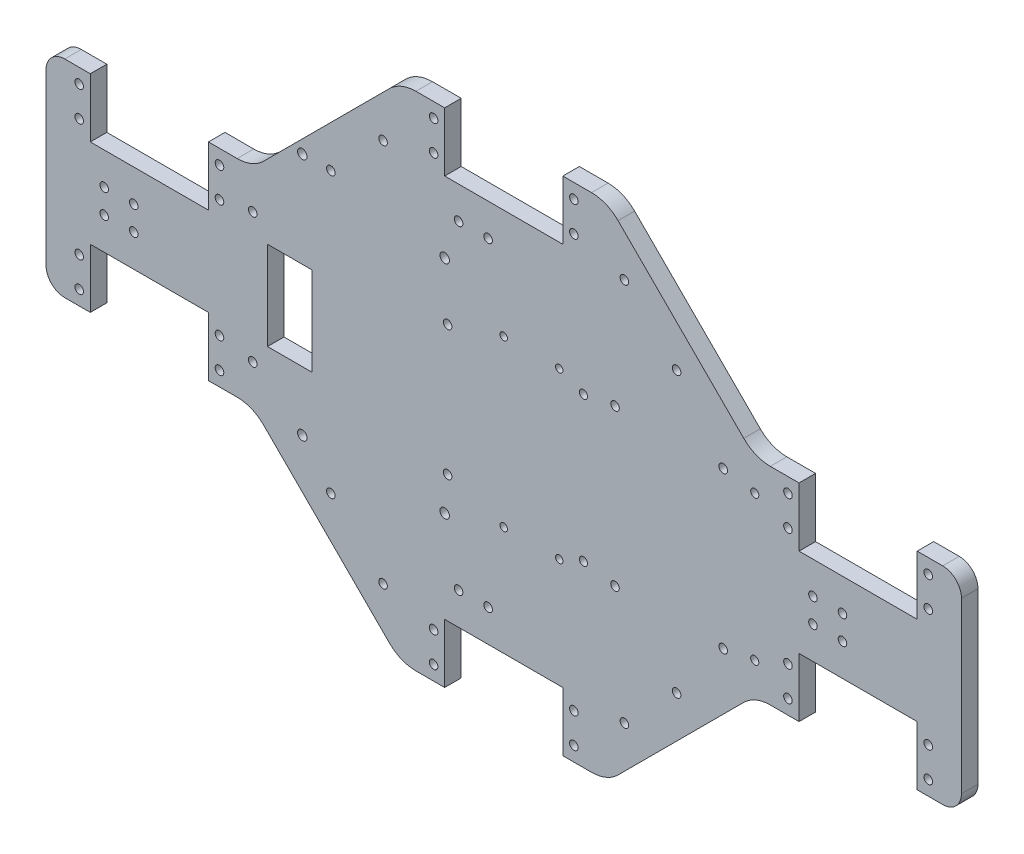
SolidWorks part; units mm, degrees
material "ABS"
ref_plane "Front" through (0, 0, 0) normal (0, 0, 1) x (1, 0, 0)
ref_plane "Top" through (0, 0, 0) normal (0, 1, 0) x (1, 0, 0)
ref_plane "Right" through (0, 0, 0) normal (1, 0, 0) x (0, 0, -1)
sketch "Esquisse1" plane through (0, 0, 0) normal (0, 0, 1) x (1, 0, 0)
  line L0 (70, -35) -> (120, -85)
  line L1 (0, 0) -> (25.8386, 0)
  line L2 (0, 0) -> (0, -35)
  line L3 (0, -35) -> (70, -35)
  line L5 (0, 0) -> (70, -35) construction
  line L6 (0, -35) -> (25.8386, 0) construction
  line L7 (120, -85) -> (190, -85)
  line L8 (190, -85) -> (240, -35)
  line L9 (240, -35) -> (310, -35)
  line L10 (310, -35) -> (310, 0)
  line L11 (310, 0) -> (25.8386, 0)
  point P0 (0, 0)
  dimension "D1" = 70
  dimension "D2" = 70
  dimension "D3" = 70
  dimension "D4" = 135
  dimension "D5" = 135
  dimension "D6" = 0
  dimension "D7" = 50
  dimension "D8" = 35
extrude "Boss.-Extru.1" add sketch "Esquisse1" along normal blind 5.6
sketch "Esquisse2" plane through (0, 0, 5.6) normal (0, 0, 1) x (1, 0, 0)
  line L0 (0, -35) -> (70, -35) construction
  line L1 (15, -15) -> (55, -15)
  line L2 (15, -15) -> (15, -35)
  line L3 (15, -35) -> (55, -35)
  line L4 (55, -15) -> (55, -35)
  line L5 (15, -15) -> (55, -35) construction
  line L6 (15, -35) -> (55, -15) construction
  line L7 (0, 0) -> (0, -35) construction
  point P0 (0, -90)
  dimension "D1" = 20
  dimension "D2" = 40
  dimension "D3" = 15
extrude "Enlèv. mat.-Extru.1" cut sketch "Esquisse2" against normal up to next
sketch "Esquisse3" plane through (0, 0, 5.6) normal (0, 0, 1) x (1, 0, 0)
  line L0 (15, -25) -> (55, -25) construction
  line L1 (15, -15) -> (15, -35) construction
  line L2 (55, -35) -> (55, -15) construction
  circle A0 centre (11.25, -30.08) radius 1.45
  circle A1 centre (58.75, -30.08) radius 1.45
  circle A2 centre (58.75, -19.92) radius 1.45
  circle A3 centre (11.25, -19.92) radius 1.45
  circle A4 centre (19.712, -4.09) radius 1.45
  circle A5 centre (29.712, -4.09) radius 1.45
  dimension "D1" = 3.75
  dimension "D2" = 5.08
  dimension "D3" = 47.5
  dimension "D4" = 2.9
  dimension "D5" = 3.75
  dimension "D6" = 2.9
  dimension "D7" = 2.9
  dimension "D8" = 10
  dimension "D9" = 8.462
  dimension "D10" = 15.83
  dimension "D11" = 0
extrude "Enlèv. mat.-Extru.2" cut sketch "Esquisse3" against normal up to next
sketch "Sketch2" plane through (0, 0, 0) normal (0, 0, 1) x (1, 0, 0)
  line L0 (120, -85) -> (190, -85) construction
  line L1 (255, -15) -> (295, -15)
  line L2 (255, -15) -> (255, -35)
  line L3 (255, -35) -> (295, -35)
  line L4 (295, -15) -> (295, -35)
  line L5 (255, -15) -> (295, -35) construction
  line L6 (255, -35) -> (295, -15) construction
  line L7 (240, -35) -> (310, -35) construction
  line L8 (310, -35) -> (310, 0) construction
  line L9 (135, -65) -> (175, -65)
  line L10 (135, -65) -> (135, -85)
  line L11 (135, -85) -> (175, -85)
  line L12 (175, -65) -> (175, -85)
  line L13 (135, -65) -> (175, -85) construction
  line L14 (135, -85) -> (175, -65) construction
  point P0 (0, -90)
  point P11 (-35, 0)
  dimension "D1" = 20
  dimension "D2" = 40
  dimension "D3" = 15
  dimension "D4" = 40
  dimension "D5" = 20
  dimension "D6" = 15
extrude "Cut-Extrude2" cut sketch "Sketch2" against normal through all and the other way through all
sketch "Sketch5" plane through (0, 0, 0) normal (0, 0, 1) x (1, 0, 0)
  line L0 (180, -75) -> (175, -75) construction
  line L1 (175, -85) -> (175, -65) construction
  line L2 (255, -25) -> (295, -25) construction
  line L4 (295, -35) -> (295, -15) construction
  line L5 (255, -15) -> (255, -35) construction
  circle A0 centre (131.25, -80.08) radius 1.45
  circle A1 centre (178.75, -80.08) radius 1.45
  circle A2 centre (178.75, -69.92) radius 1.45
  circle A3 centre (131.25, -69.92) radius 1.45
  circle A4 centre (251.25, -30.08) radius 1.45
  circle A5 centre (298.75, -30.08) radius 1.45
  circle A6 centre (298.75, -19.92) radius 1.45
  circle A7 centre (251.25, -19.92) radius 1.45
  circle A8 centre (139.712, -54.09) radius 1.45
  circle A9 centre (149.712, -54.09) radius 1.45
  circle A10 centre (259.712, -4.09) radius 1.45
  circle A11 centre (269.712, -4.09) radius 1.45
  dimension "D1" = 5.08
  dimension "D2" = 5.08
  dimension "D3" = 47.5
  dimension "D4" = 2.9
  dimension "D5" = 3.75
  dimension "D10" = 2.9
  dimension "D11" = 2.9
  dimension "D12" = 2.9
  dimension "D16" = 2.9
  dimension "D17" = 2.9
  dimension "D6" = 5.08
  dimension "D7" = 5.08
  dimension "D8" = 3.75
  dimension "D9" = 3.75
  dimension "D13" = 10
  dimension "D14" = 8.462
  dimension "D15" = 15.83
  dimension "D18" = 8.462
  dimension "D19" = 15.83
  dimension "D20" = 10
  dimension "D21" = 0
  dimension "D22" = 0
extrude "Cut-Extrude4" cut sketch "Sketch5" along normal through all
mirror "Mirror1" about plane through (0, 0, 0) normal (0, 1, 0) of "Cut-Extrude4", "Cut-Extrude2", "Enlèv. mat.-Extru.1", "Enlèv. mat.-Extru.2", "Boss.-Extru.1"
sketch "Esquisse4" plane through (0, 0, 5.6) normal (0, 0, 1) x (1, 0, 0)
  line L0 (182, 24.5) -> (240, 24.5) construction
  line L1 (240, 24.5) -> (240, -24.5) construction
  line L2 (240, -24.5) -> (182, -24.5) construction
  line L3 (0, 0) -> (310, 0) construction
  line L4 (0, 35) -> (0, -35) construction
  line L5 (310, -35) -> (310, 35) construction
  line L6 (255, 15) -> (255, 35) construction
  circle A0 centre (182, -24.5) radius 1.375
  circle A4 centre (240, -24.5) radius 1.375
  circle A5 centre (240, 24.5) radius 1.375
  circle A6 centre (182, 24.5) radius 1.375
  point P14 (240, 0)
  dimension "D1" = 2.75
  dimension "D6" = 15
  dimension "D2" = 2
  dimension "D3" = 58
  dimension "D4" = 49
  dimension "D5" = 2
extrude "Enlèv. mat.-Extru.4" cut sketch "Esquisse4" against normal through all
sketch "Esquisse6" plane through (0, 0, 0) normal (0, 0, -1) x (-1, 0, 0)
  line L0 (0, 0) -> (-385.37, 0) construction
  line L1 (-229.315, 26.415) -> (-192.685, 26.415) construction
  line L2 (-192.685, 26.415) -> (-192.685, -26.415) construction
  line L3 (-192.685, -26.415) -> (-229.315, -26.415) construction
  line L4 (-182, 24.5) -> (-240, 24.5) construction
  line L5 (-211, 24.5) -> (-211, 26.415) construction
  circle A0 centre (-192.685, -26.415) radius 1.45
  circle A4 centre (-229.315, -26.415) radius 1.45
  circle A5 centre (-229.315, 26.415) radius 1.45
  circle A6 centre (-192.685, 26.415) radius 1.45
  point P5 (-192.685, 0)
  dimension "D1" = 2.9
  dimension "D2" = 2
  dimension "D3" = 36.63
  dimension "D4" = 52.83
  dimension "D5" = 2
extrude "Enlèv. mat.-Extru.6" cut sketch "Esquisse6" against normal through all
sketch "Esquisse8" plane through (0, 0, 0) normal (0, 0, -1) x (-1, 0, 0)
  line L0 (-173.8, 27.95) -> (-155, 27.95) construction
  line L1 (-155, 27.95) -> (-155, -27.95) construction
  line L2 (-155, -27.95) -> (-173.8, -27.95) construction
  line L3 (0, 0) -> (-310, 0) construction
  line L4 (-310, -35) -> (-310, 35) construction
  line L5 (-55, 35) -> (-55, 15) construction
  circle A0 centre (-155, 27.95) radius 1.25
  circle A1 centre (-173.8, 27.95) radius 1.25
  circle A2 centre (-173.8, -27.95) radius 1.25
  circle A3 centre (-155, -27.95) radius 1.25
  point P16 (-155, 0)
  dimension "D1" = 2.5
  dimension "D2" = 18.8
  dimension "D3" = 55.9
  dimension "D6" = 100
  dimension "D4" = 2
  dimension "D5" = 2
extrude "Enlèv. mat.-Extru.7" cut sketch "Esquisse8" against normal through all
sketch "Esquisse9" plane through (0, 0, 0) normal (0, 0, -1) x (-1, 0, 0)
  line L0 (-135, 65) -> (-135, 85) construction
  line L2 (-175, 65) -> (-135, 65) construction
  circle A1 centre (-135, -33.88) radius 1.6
  circle A2 centre (-86.78, -35.11) radius 1.6
  circle A3 centre (-86.78, 47.36) radius 1.6
  circle A4 centre (-135, 41) radius 1.6
  dimension "D8" = 1.23
  dimension "D1" = 74.88
  dimension "D2" = 82.47
  dimension "D3" = 48.22
  dimension "D4" = 48.22
  dimension "D5" = 48.22
  dimension "D6" = 24
extrude "Enlèv. mat.-Extru.8" cut sketch "Esquisse9" against normal through all
sketch "Sketch6" plane through (0, 0, 5.6) normal (0, 0, 1) x (1, 0, 0)
  line L0 (0, 0) -> (310, 0) construction
  line L1 (75, -15) -> (90, -15)
  line L2 (75, -15) -> (75, 15)
  line L3 (75, 15) -> (90, 15)
  line L4 (90, -15) -> (90, 15)
  line L5 (310, -35) -> (310, 35) construction
  line L6 (55, 15) -> (15, 15) construction
  line L7 (55, 35) -> (55, 15) construction
  point P9 (75, 0)
  dimension "D1" = 20
  dimension "D2" = 15
extrude "Cut-Extrude5" cut sketch "Sketch6" against normal blind 10
sketch "Sketch7" plane through (0, 0, 0) normal (0, 0, -1) x (-1, 0, 0)
  line L0 (0, 0) -> (-310, 0) construction
  line L1 (-70, 22) -> (-136, 22) construction
  line L2 (-70, 22) -> (-70, -22) construction
  line L3 (-70, -22) -> (-136, -22) construction
  line L4 (-136, 22) -> (-136, -22) construction
  line L5 (-70, 22) -> (-136, -22) construction
  line L6 (-70, -22) -> (-136, 22) construction
  line L7 (0, 35) -> (0, -35) construction
  line L8 (-310, -35) -> (-310, 35) construction
  line L10 (-75, 15) -> (-75, -15) construction
  circle A0 centre (-70, -22) radius 1.45
  circle A1 centre (-136, -22) radius 1.45
  circle A2 centre (-136, 22) radius 1.45
  circle A3 centre (-70, 22) radius 1.45
  point P4 (-103, 0)
  dimension "D1" = 2.9
  dimension "D2" = 66
  dimension "D3" = 44
  dimension "D4" = 5
extrude "Cut-Extrude6" cut sketch "Sketch7" against normal up to surface (5.6 mm away) up to face at (82.5, 0, 5.6)
ref_plane "Plan1" through (155, 0, 0) normal (-1, 0, 0) x (0, 0, 1)
ref_plane "Plan2" through (0, 0, 0) normal (0, 1, 0) x (1, 0, 0)
sketch "Esquisse12" plane through (0, 0, 5.6) normal (0, 0, 1) x (1, 0, 0)
  line L0 (96.4645, 47.3223) -> (114.1421, 65) construction
  line L1 (155, 24.0954) -> (155, -24.0954) construction
  line L2 (22.5792, 0) -> (-22.5792, 0) construction
  line L3 (70, 35) -> (120, 85) construction
  line L4 (175, 65) -> (135, 65) construction
  circle A0 centre (114.1421, 65) radius 1.45
  circle A1 centre (96.4645, 47.3223) radius 1.45
  circle A2 centre (213.5355, 47.3223) radius 1.45
  circle A3 centre (195.8579, 65) radius 1.45
  circle A4 centre (213.5355, -47.3223) radius 1.45
  circle A5 centre (195.8579, -65) radius 1.45
  circle A6 centre (114.1421, -65) radius 1.45
  circle A7 centre (96.4645, -47.3223) radius 1.45
  dimension "D1" = 2.9
  dimension "D2" = 2.9
  dimension "D3" = 25
  dimension "D4" = 10
extrude "Enlèv. mat.-Extru.11" cut sketch "Esquisse12" against normal through all
fillet "Fillet1" radius 6.35 4 edges at (310, 35, 2.8) (310, -35, 2.8) (0, -35, 2.8) (0, 35, 2.8)
fillet "Fillet2" radius 12.7 8 edges at (120, -85, 2.8) (70, -35, 2.8) (190, -85, 2.8) (240, -35, 2.8) (240, 35, 2.8) (190, 85, 2.8) (120, 85, 2.8) (70, 35, 2.8)
